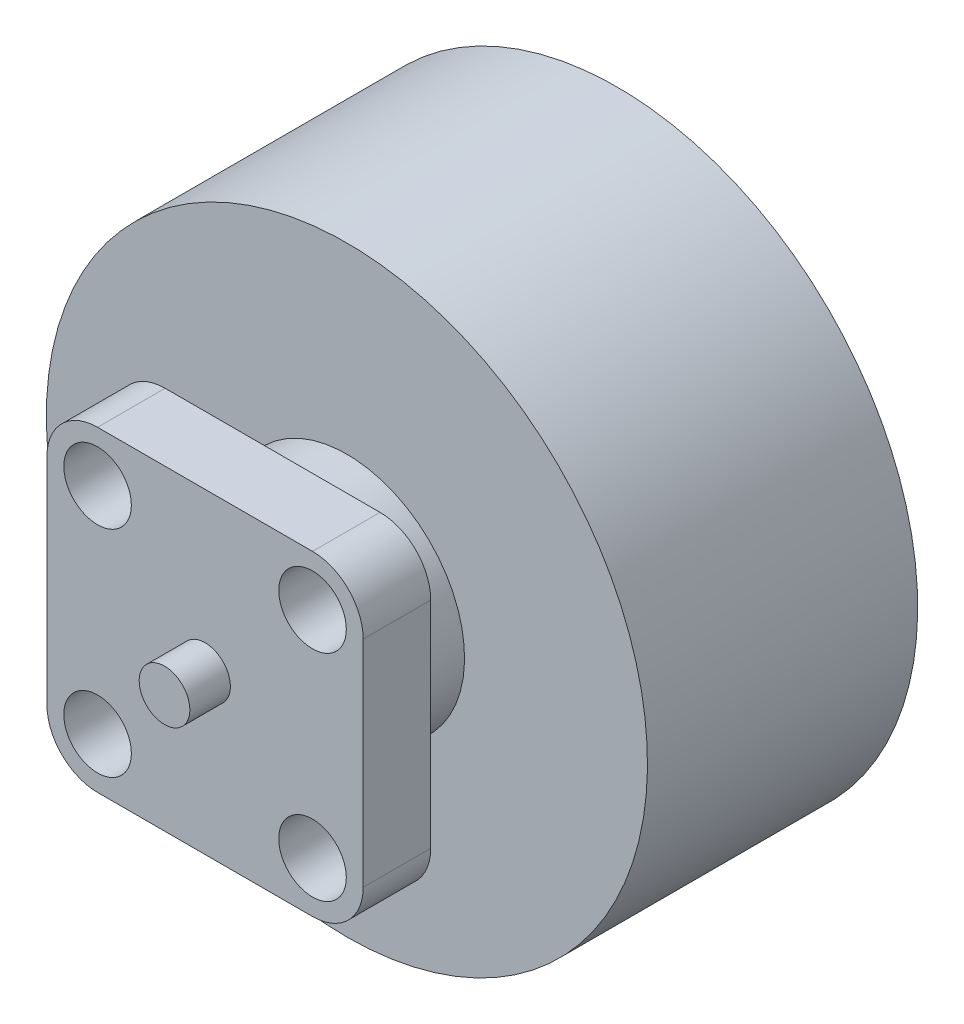
SolidWorks part; units mm, degrees
ref_plane "Front Plane" through (0, 0, 0) normal (0, 0, 1) x (1, 0, 0)
ref_plane "Top Plane" through (0, 0, 0) normal (0, 1, 0) x (1, 0, 0)
ref_plane "Right Plane" through (0, 0, 0) normal (1, 0, 0) x (0, 0, -1)
sketch "Sketch1" plane through (0, 0, 0) normal (1, 0, 0) x (0, 0, -1)
  line L0 (-1.2, 0) -> (16.4, 0)
  line L2 (-1.2, 0.75) -> (16.4, 0.75)
  line L3 (-1.2, 0.75) -> (-1.2, -0.75)
  line L4 (-1.2, -0.75) -> (16.4, -0.75)
  line L5 (16.4, 0.75) -> (16.4, -0.75)
  line L6 (4.2, 0) -> (12.2, 0)
  line L7 (4.2, 0) -> (4.2, 8.9)
  line L8 (4.2, 8.9) -> (12.2, 8.9)
  line L9 (12.2, 0) -> (12.2, 8.9)
  line L10 (0, 0) -> (4.2, 0)
  line L11 (0, 0) -> (0, 3.4836)
  line L12 (0, 3.4836) -> (4.2, 3.4836)
  line L13 (4.2, 0) -> (4.2, 3.4836)
  dimension "D1" = 17.6
  dimension "D2" = 1.5
  dimension "D3" = 1.2
  dimension "D4" = 4.2
  dimension "D5" = 8
  dimension "D6" = 8.9
revolve "Revolve1" add sketch "Sketch1" angle 360 about L0 region at (0, 0.375, 0.6) region at (0, 0.375, -2.1) region at (0, 0.375, -8.2) region at (0, 2.1168, -2.1) region at (0, 0.375, -14.3) region at (0, 4.825, -8.2)
sketch "Sketch2" plane through (0, 0, 0) normal (0, 0, 1) x (1, 0, 0)
  line L1 (0, 0) -> (4.5, 0) construction
  line L3 (-4.682, -4.682) -> (4.682, -4.682)
  line L4 (-4.682, -4.682) -> (-4.682, 4.682)
  line L5 (-4.682, 4.682) -> (4.682, 4.682)
  line L6 (4.682, -4.682) -> (4.682, 4.682)
  line L7 (-4.682, -4.682) -> (4.682, 4.682) construction
  line L8 (-4.682, 4.682) -> (4.682, -4.682) construction
  circle A0 centre (3.182, 3.182) radius 1
  circle A1 centre (0, 0) radius 4.5 construction
  circle A2 centre (3.182, -3.182) radius 1
  circle A3 centre (-3.182, -3.182) radius 1
  circle A4 centre (-3.182, 3.182) radius 1
  point P15 (0, 0)
  dimension "D1" = 2
  dimension "D2" = 9
  dimension "D3" = 1.5
  dimension "D4" = 4
extrude "Boss-Extrude1" add sketch "Sketch2" against normal blind 2
fillet "Fillet1" radius 1.5 4 edges at (4.682, -4.682, -1) (-4.682, -4.682, -1) (-4.682, 4.682, -1) (4.682, 4.682, -1)
sketch "Sketch3" plane through (0, 0, -12.2) normal (0, 0, -1) x (-1, 0, 0)
  circle A0 centre (0, 2.5) radius 1
  circle A1 centre (0, 0) radius 2.5 construction
  circle A2 centre (2.5, 0) radius 1
  circle A3 centre (0, -2.5) radius 1
  circle A4 centre (-2.5, 0) radius 1
  point P13 (0, 0)
  dimension "D1" = 2
  dimension "D2" = 5
  dimension "D3" = 4
extrude "Cut-Extrude1" cut sketch "Sketch3" against normal blind 2
